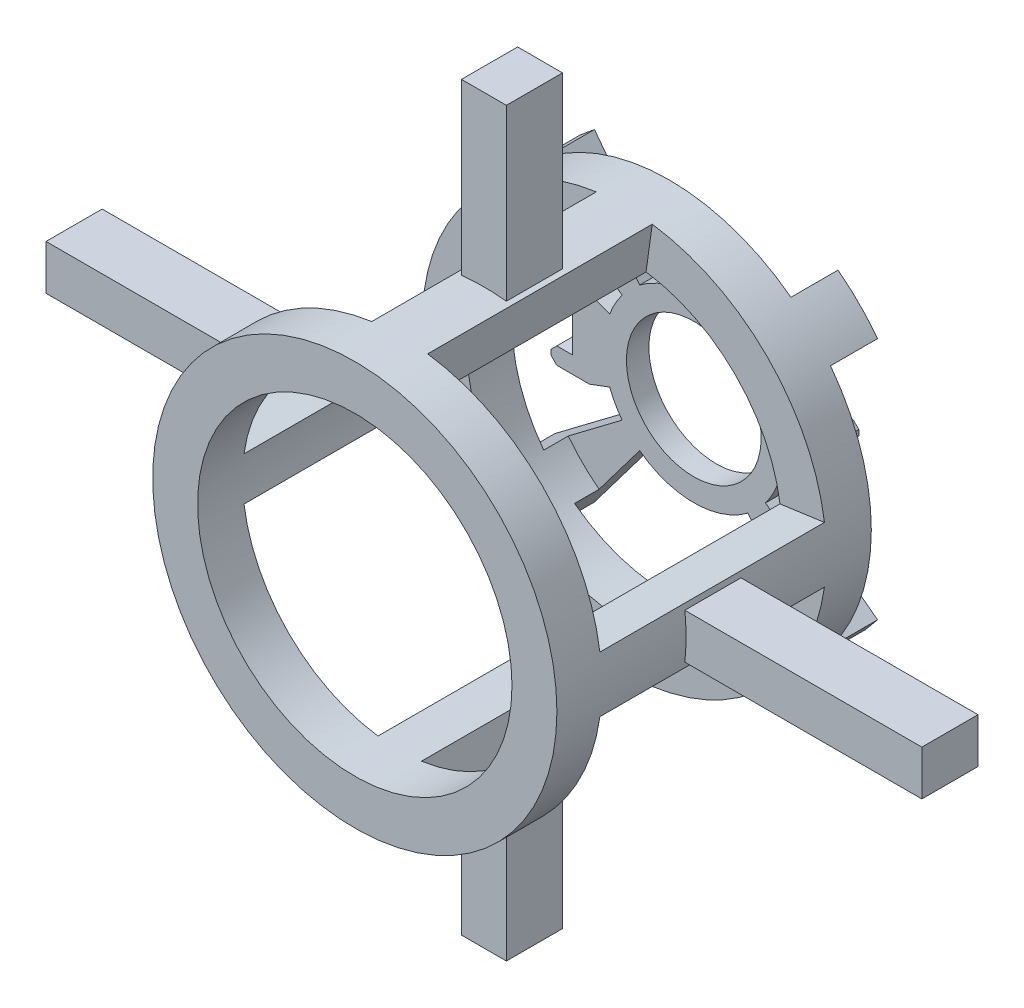
SolidWorks part; units mm, degrees
ref_plane "Front Plane" through (0, 0, 0) normal (0, 0, 1) x (1, 0, 0)
ref_plane "Top Plane" through (0, 0, 0) normal (0, 1, 0) x (1, 0, 0)
ref_plane "Right Plane" through (0, 0, 0) normal (1, 0, 0) x (0, 0, -1)
sketch "Sketch1" plane through (0, 0, 0) normal (0, 0, 1) x (1, 0, 0)
  line L0 (-2.492, -17.8267) -> (-1.9382, -13.8652)
  line L1 (-17.8267, -2.492) -> (-13.8652, -1.9382)
  line L2 (-2.492, 17.8267) -> (-1.9382, 13.8652)
  line L3 (-14, 0) -> (14, 0) construction
  line L4 (17.8267, -2.492) -> (13.8652, -1.9382)
  line L5 (1.9382, 13.8652) -> (2.492, 17.8267)
  line L6 (0, -14) -> (0, 14) construction
  line L7 (1.9382, -13.8652) -> (2.492, -17.8267)
  line L8 (-13.8652, 1.9382) -> (-17.8267, 2.492)
  line L9 (13.8652, 1.9382) -> (17.8267, 2.492)
  arc A0 (-1.9382, -13.8652) -> (1.9382, -13.8652) centre (0, 0) ccw
  arc A1 (-2.492, -17.8267) -> (2.492, -17.8267) centre (0, 0) ccw
  arc A2 (17.8267, -2.492) -> (17.8267, 2.492) centre (0, 0) ccw
  arc A3 (13.8652, -1.9382) -> (13.8652, 1.9382) centre (0, 0) ccw
  arc A4 (2.492, 17.8267) -> (-2.492, 17.8267) centre (0, 0) ccw
  arc A5 (1.9382, 13.8652) -> (-1.9382, 13.8652) centre (0, 0) ccw
  arc A6 (-17.8267, 2.492) -> (-17.8267, -2.492) centre (0, 0) ccw
  arc A7 (-13.8652, 1.9382) -> (-13.8652, -1.9382) centre (0, 0) ccw
  dimension "D1" = 28
  dimension "D2" = 36
  dimension "D3" = 5
extrude "Boss-Extrude1" add sketch "Sketch1" along normal blind 10 and the other way blind 10
sketch "Sketch2" plane through (0, 0, 10) normal (0, 0, 1) x (1, 0, 0)
  circle A0 centre (0, 0) radius 14
  circle A1 centre (0, 0) radius 18
extrude "Boss-Extrude2" add sketch "Sketch2" along normal blind 4
sketch "Sketch3" plane through (0, 0, -10) normal (0, 0, -1) x (-1, 0, 0)
  circle A0 centre (0, 0) radius 14
  circle A1 centre (0, 0) radius 18
extrude "Boss-Extrude3" add sketch "Sketch3" along normal blind 4
sketch "Sketch4" plane through (0, 0, -14) normal (0, 0, -1) x (-1, 0, 0)
  line L0 (-3.1033, 3.1033) -> (3.1033, -3.1033) construction
  line L1 (0, 0) -> (0, 14) construction
  line L2 (3.7591, 3.7591) -> (-6.1607, -6.1607) construction
  line L3 (10.8433, -14.3674) -> (8.4337, -11.1747)
  line L4 (-10.8433, -14.3674) -> (-8.4337, -11.1747)
  line L5 (14.3674, -10.8433) -> (11.1747, -8.4337)
  line L6 (14.3674, 10.8433) -> (11.1747, 8.4337)
  line L7 (8.4337, 11.1747) -> (10.8433, 14.3674)
  line L8 (-8.4337, 11.1747) -> (-10.8433, 14.3674)
  line L9 (-11.1747, -8.4337) -> (-14.3674, -10.8433)
  line L10 (-11.1747, 8.4337) -> (-14.3674, 10.8433)
  circle A0 centre (0, 0) radius 14 construction
  arc A1 (-11.1747, -8.4337) -> (-8.4337, -11.1747) centre (0, 0) ccw
  circle A2 centre (0, 0) radius 18 construction
  arc A3 (-14.3674, -10.8433) -> (-10.8433, -14.3674) centre (0, 0) ccw
  arc A4 (10.8433, -14.3674) -> (14.3674, -10.8433) centre (0, 0) ccw
  arc A5 (8.4337, -11.1747) -> (11.1747, -8.4337) centre (0, 0) ccw
  arc A6 (14.3674, 10.8433) -> (10.8433, 14.3674) centre (0, 0) ccw
  arc A7 (11.1747, 8.4337) -> (8.4337, 11.1747) centre (0, 0) ccw
  arc A8 (-8.4337, 11.1747) -> (-11.1747, 8.4337) centre (0, 0) ccw
  arc A9 (-10.8433, 14.3674) -> (-14.3674, 10.8433) centre (0, 0) ccw
  point P1 (0, 0)
  point P16 (0, 0)
  point P19 (0, 0)
  point P23 (0, 0)
  point P25 (0, 0)
  point P31 (-12.7279, 12.7279)
  point P34 (-12.7279, -12.7279)
  point P35 (12.7279, 12.7279)
  point P36 (12.7279, -12.7279)
  dimension "D1" = 45
  dimension "D2" = 5
extrude "Boss-Extrude4" add sketch "Sketch4" along normal blind 2.19
sketch "Sketch5" plane through (0, 0, -16.19) normal (0, 0, -1) x (-1, 0, 0)
  line L0 (-10.8433, 14.3674) -> (-4.8192, 6.3855)
  line L1 (4.8192, -6.3855) -> (10.8433, -14.3674)
  line L2 (-14.3674, 10.8433) -> (-6.3855, 4.8192)
  line L3 (11.3, 0) -> (-11.3, 0) construction
  line L4 (14.3674, 10.8433) -> (6.3855, 4.8192)
  line L5 (6.3855, -4.8192) -> (14.3674, -10.8433)
  line L6 (10.8433, 14.3674) -> (4.8192, 6.3855)
  line L7 (-6.3855, -4.8192) -> (-14.3674, -10.8433)
  line L8 (-4.8192, -6.3855) -> (-10.8433, -14.3674)
  line L9 (-11.7, 1.5) -> (-11.3, 1.5) construction
  line L10 (-11.7, 1.5) -> (-11.7, -1.5) construction
  line L11 (-11.7, -1.5) -> (-11.3, -1.5) construction
  line L12 (-11.3, 1.5) -> (-11.3, -1.5) construction
  line L13 (-10.8, 2) -> (-10.8, -2)
  line L14 (11.3, 1.5) -> (11.7, 1.5) construction
  line L15 (11.3, 1.5) -> (11.3, -1.5) construction
  line L16 (11.3, -1.5) -> (11.7, -1.5) construction
  line L17 (11.7, 1.5) -> (11.7, -1.5) construction
  line L18 (-12.2, -2) -> (-10.8, -2)
  line L19 (-12.2, 2) -> (-10.8, 2) construction
  line L20 (-12.2, 2) -> (-10.8, 2)
  line L21 (10.8, -2) -> (12.2, -2)
  line L22 (10.8, 2) -> (12.2, 2) construction
  line L23 (10.8, 2) -> (12.2, 2)
  line L24 (10.8, 2) -> (10.8, -2)
  line L25 (9.3, -3.5) -> (7.4873, -2.8178)
  line L26 (9.3, 3.5) -> (7.4873, 2.8178)
  line L27 (-7.4873, 2.8178) -> (-9.3, 3.5)
  line L28 (-7.4873, -2.8178) -> (-9.3, -3.5)
  line L29 (-12.2, 2) -> (-12.2, -2) construction
  line L30 (-12.2, -3.5) -> (-9.3, -3.5)
  line L31 (-12.2, -2) -> (-10.8, -2) construction
  line L32 (-12.2, 3.5) -> (-9.3, 3.5)
  line L33 (-12.7, 3) -> (-12.7, 2.5)
  line L34 (9.3, -3.5) -> (12.2, -3.5)
  line L35 (12.2, 2) -> (12.2, -2) construction
  line L36 (9.3, 3.5) -> (12.2, 3.5)
  line L37 (10.8, -2) -> (12.2, -2) construction
  line L38 (-12.7, -2.5) -> (-12.7, -3)
  line L39 (12.7, 3) -> (12.7, 2.5)
  line L40 (12.7, -2.5) -> (12.7, -3)
  line L41 (-12.2, 3.5) -> (-12.7, 3)
  line L42 (-12.7, 2.5) -> (-12.2, 2)
  line L43 (-12.7, -2.5) -> (-12.2, -2)
  line L44 (-12.7, -3) -> (-12.2, -3.5)
  line L45 (12.2, 3.5) -> (12.7, 3)
  line L46 (12.2, 2) -> (12.7, 2.5)
  line L47 (12.2, -2) -> (12.7, -2.5)
  line L48 (12.7, -3) -> (12.2, -3.5)
  circle A0 centre (0, 0) radius 6
  arc A1 (6.3855, -4.8192) -> (7.4873, -2.8178) centre (0, 0) ccw
  arc A2 (-4.8192, -6.3855) -> (4.8192, -6.3855) centre (0, 0) ccw
  arc A3 (-6.3855, 4.8192) -> (-7.4873, 2.8178) centre (0, 0) ccw
  arc A4 (4.8192, 6.3855) -> (-4.8192, 6.3855) centre (0, 0) ccw
  arc A5 (-10.8433, 14.3674) -> (-14.3674, 10.8433) centre (0, 0) ccw
  arc A6 (-14.3674, -10.8433) -> (-10.8433, -14.3674) centre (0, 0) ccw
  arc A7 (10.8433, -14.3674) -> (14.3674, -10.8433) centre (0, 0) ccw
  arc A8 (14.3674, 10.8433) -> (10.8433, 14.3674) centre (0, 0) ccw
  arc A12 (-7.4873, -2.8178) -> (-6.3855, -4.8192) centre (0, 0) ccw
  arc A13 (7.4873, 2.8178) -> (6.3855, 4.8192) centre (0, 0) ccw
  point P34 (0, 0)
  point P38 (-12.7, 2)
  point P39 (-12.7, -2)
  point P48 (12.7, 2)
  point P49 (12.7, -3.5)
  point P50 (-12.7, 3.5)
  point P51 (0, 0)
  point P53 (12.7, -2)
  point P55 (0, 0)
  point P66 (-12.7, -3.5)
  point P76 (12.7, 3.5)
  dimension "D1" = 12
  dimension "D2" = 2
  dimension "D3" = 0.4
  dimension "D4" = 3
  dimension "D5" = 22.6
  dimension "D7" = 1
  dimension "D8" = 1.5
  dimension "D9" = 1.5
  dimension "D6" = 0.5
extrude "Boss-Extrude5" add sketch "Sketch5" along normal blind 2
sketch "Sketch6" plane through (0, 0, 0) normal (0, 0, 1) x (1, 0, 0)
  line L0 (-16, 0) -> (16, 0) construction
  line L1 (-39, 2) -> (-15.8745, 2)
  line L2 (-39, 2) -> (-39, -2)
  line L3 (-39, -2) -> (-15.8745, -2)
  line L4 (39, 2) -> (39, -2)
  line L5 (-2, 33) -> (2, 33)
  line L6 (-2, 33) -> (-2, 15.8745)
  line L7 (-2, -33) -> (2, -33)
  line L8 (2, 33) -> (2, 15.8745)
  line L10 (0, -16) -> (0, 16) construction
  line L14 (15.8745, 2) -> (39, 2)
  line L15 (15.8745, -2) -> (39, -2)
  line L16 (2, -15.8745) -> (2, -33)
  line L17 (-2, -15.8745) -> (-2, -33)
  arc A0 (-15.8745, 2) -> (-15.8745, -2) centre (0, 0) ccw
  arc A1 (2, 15.8745) -> (-2, 15.8745) centre (0, 0) ccw
  arc A2 (15.8745, -2) -> (15.8745, 2) centre (0, 0) ccw
  arc A3 (-2, -15.8745) -> (2, -15.8745) centre (0, 0) ccw
  dimension "D4" = 32
  dimension "D1" = 4
  dimension "D2" = 78
  dimension "D3" = 66
extrude "Boss-Extrude6" add sketch "Sketch6" along normal blind 2.5 and the other way blind 2.5
